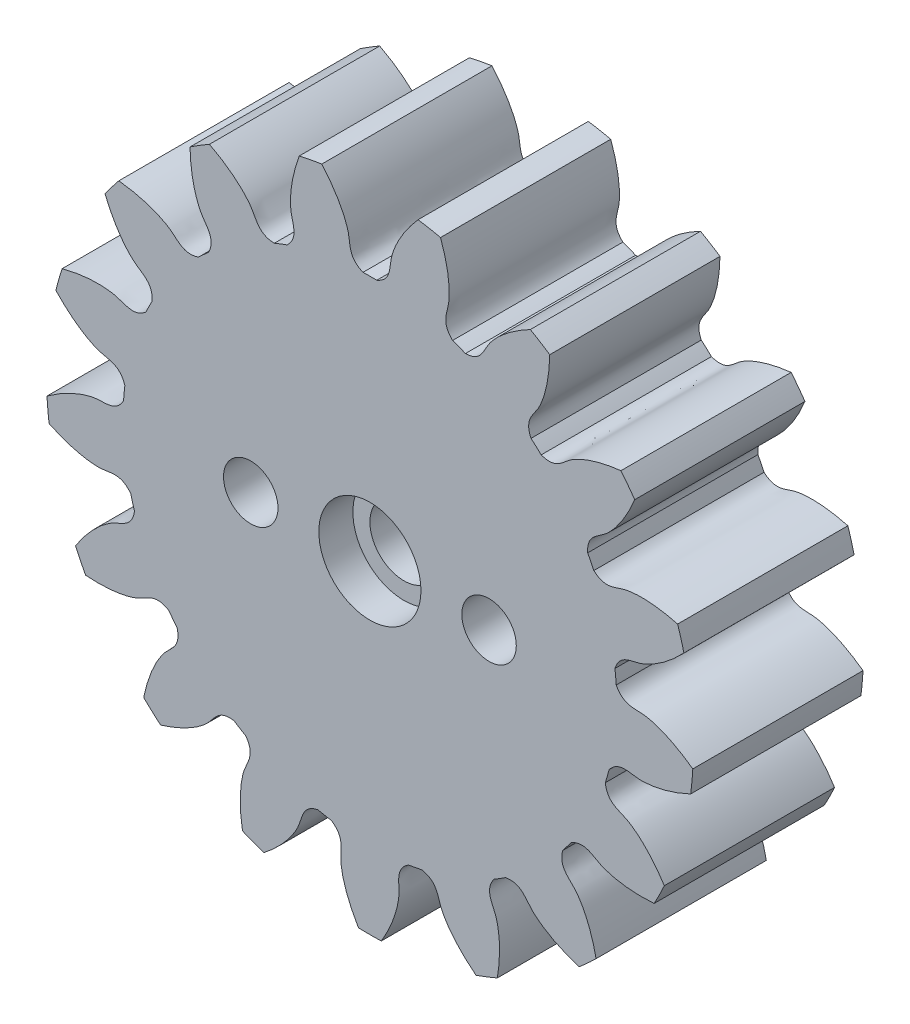
SolidWorks part; units mm, degrees
ref_plane "前视基准面" through (0, 0, 0) normal (0, 0, 1) x (1, 0, 0)
ref_plane "上视基准面" through (0, 0, 0) normal (0, 1, 0) x (1, 0, 0)
ref_plane "右视基准面" through (0, 0, 0) normal (1, 0, 0) x (0, 0, -1)
other "Configuration Table"
sketch "草图1" plane through (0, 0, 0) normal (0, 0, 1) x (1, 0, 0)
  circle A0 centre (0, 0) radius 19
extrude "凸台-拉伸1" add sketch "草图1" along normal blind 10
ref_axis "基准轴1" through (0, 0, -0.25) along (0, 0, 1)
sketch "草图2" plane through (0, 0, 0) normal (0, 0, 1) x (1, 0, 0)
  line L0 (0, 0) -> (0, 19) construction
  circle A0 centre (0, 0) radius 19 construction
  arc A1 (0.4034, 14.4944) -> (-0.4034, 14.4944) centre (0, 0) ccw
  arc A2 (6.2313, 21.4814) -> (-6.2313, 21.4814) centre (0, 0) ccw
  spline S0 degree 3 poles (0.4034, 14.4944) (1.2558, 14.8496) (1.1324, 15.5096) (1.2766, 16.1296) (1.29, 16.1823) (1.306, 16.2408) (1.3251, 16.3052) (1.3474, 16.3752) (1.3731, 16.4508) (1.4025, 16.5319) (1.4359, 16.6184) (1.4733, 16.7101) (1.5152, 16.8068) (1.5616, 16.9086) (1.6128, 17.0151) (1.669, 17.1264) (1.7304, 17.2421) (1.7972, 17.3621) (1.8696, 17.4863) (1.9478, 17.6145) (2.032, 17.7465) (2.1224, 17.8821) (2.2191, 18.0211) (2.3223, 18.1634) (2.4322, 18.3086) (2.5489, 18.4566) (2.6727, 18.6072) (2.8035, 18.7601) (2.9417, 18.9152) (3.0873, 19.0722) (3.2404, 19.2308) (3.4012, 19.3908) (3.5698, 19.552) (3.7462, 19.7141) (3.9307, 19.8769) (4.1233, 20.0401) (4.324, 20.2035) (4.533, 20.3667) (4.7503, 20.5295) (4.9761, 20.6917) (5.2103, 20.853) (5.453, 21.0131) (5.7916, 21.2269) (6.0532, 21.3811) (6.2313, 21.4814) knots 0 0 0 0 0.193883 0.199024 0.204851 0.211363 0.21856 0.226443 0.235011 0.244265 0.254205 0.264829 0.27614 0.288136 0.300817 0.314184 0.328236 0.342973 0.358397 0.374505 0.391299 0.408779 0.426944 0.445795 0.465331 0.485552 0.506459 0.528051 0.550329 0.573293 0.596941 0.621276 0.646296 0.672001 0.698392 0.725468 0.753229 0.781677 0.810809 0.840627 0.871131 0.90232 0.934195 1 1 1 1
  spline S1 degree 3 poles (-0.4034, 14.4944) (-1.2558, 14.8496) (-1.1324, 15.5096) (-1.2766, 16.1296) (-1.29, 16.1823) (-1.306, 16.2408) (-1.3251, 16.3052) (-1.3474, 16.3752) (-1.3731, 16.4508) (-1.4025, 16.5319) (-1.4359, 16.6184) (-1.4733, 16.7101) (-1.5152, 16.8068) (-1.5616, 16.9086) (-1.6128, 17.0151) (-1.669, 17.1264) (-1.7304, 17.2421) (-1.7972, 17.3621) (-1.8696, 17.4863) (-1.9478, 17.6145) (-2.032, 17.7465) (-2.1224, 17.8821) (-2.2191, 18.0211) (-2.3223, 18.1634) (-2.4322, 18.3086) (-2.5489, 18.4566) (-2.6727, 18.6072) (-2.8035, 18.7601) (-2.9417, 18.9152) (-3.0873, 19.0722) (-3.2404, 19.2308) (-3.4012, 19.3908) (-3.5698, 19.552) (-3.7462, 19.7141) (-3.9307, 19.8769) (-4.1233, 20.0401) (-4.324, 20.2035) (-4.533, 20.3667) (-4.7503, 20.5295) (-4.9761, 20.6917) (-5.2103, 20.853) (-5.453, 21.0131) (-5.7916, 21.2269) (-6.0532, 21.3811) (-6.2313, 21.4814) knots 0 0 0 0 0.193883 0.199024 0.204851 0.211363 0.21856 0.226443 0.235011 0.244265 0.254205 0.264829 0.27614 0.288136 0.300817 0.314184 0.328236 0.342973 0.358397 0.374505 0.391299 0.408779 0.426944 0.445795 0.465331 0.485552 0.506459 0.528051 0.550329 0.573293 0.596941 0.621276 0.646296 0.672001 0.698392 0.725468 0.753229 0.781677 0.810809 0.840627 0.871131 0.90232 0.934195 1 1 1 1
extrude "切除-拉伸1" cut sketch "草图2" along normal through all
pattern_circular "阵列(圆周)1" count 17 every 21.176 about axis through (0, 0, -0.25) along (0, 0, 1) of "切除-拉伸1"
sketch "草图3" plane through (0, 0, 0) normal (0, 0, 1) x (1, 0, 0)
  circle A0 centre (0, 0) radius 17 construction
  dimension "Dn" = 34
sketch "草图4" plane through (0, 0, 10) normal (0, 0, 1) x (1, 0, 0)
  circle A0 centre (7, 0) radius 1.6
  circle A1 centre (-7, 0) radius 1.6
  circle A2 centre (0, 0) radius 2
  dimension "D1" = 3.2
  dimension "D2" = 3.2
  dimension "D6" = 4
  dimension "D3" = 7
  dimension "D4" = 7
  dimension "D5" = 14
extrude "切除-拉伸2" cut sketch "草图4" against normal through all
sketch "草图5" plane through (0, 0, 10) normal (0, 0, 1) x (1, 0, 0)
  circle A0 centre (0, 0) radius 3
  dimension "D1" = 6
extrude "切除-拉伸3" cut sketch "草图5" against normal blind 2
